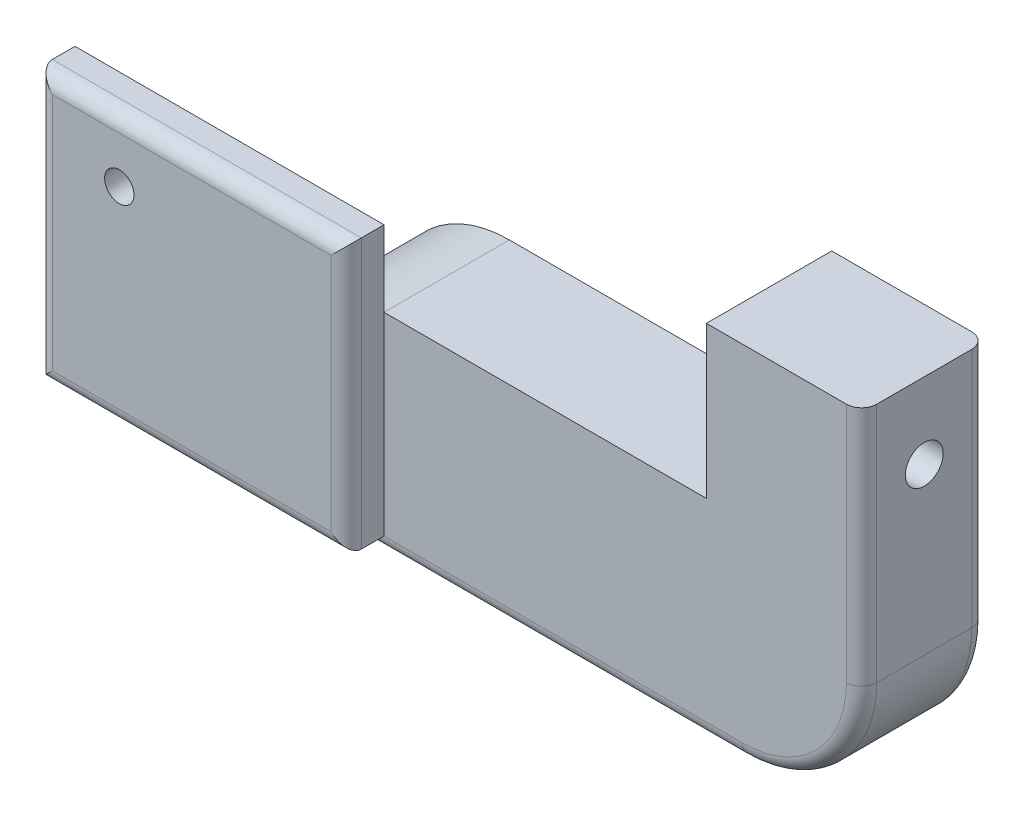
SolidWorks part; units mm, degrees
ref_plane "XY" through (0, 0, 0) normal (0, 0, 1) x (1, 0, 0)
ref_plane "XZ" through (0, 0, 0) normal (0, 1, 0) x (1, 0, 0)
ref_plane "YZ" through (0, 0, 0) normal (1, 0, 0) x (0, 0, -1)
ref_axis "X" through (-88.3595, 0, 0) along (1, 0, 0)
ref_axis "Y" through (0, -20.5837, 0) along (0, 1, 0)
ref_axis "Z" through (0, 0, 28.7175) along (0, 0, -1)
sketch "Sketch1" plane through (0, 0, 0) normal (0, 0, 1) x (1, 0, 0)
  line L1 (-50, -17.5) -> (30, -17.5)
  line L2 (-50, -17.5) -> (-50, -2.5)
  line L3 (-30, 17.5) -> (24, 17.5)
  line L4 (50, 2.5) -> (50, 17.5)
  line L5 (-50, -17.5) -> (50, 17.5) construction
  line L6 (-50, 17.5) -> (50, -17.5) construction
  line L8 (24, 17.5) -> (24, 42.9)
  line L9 (24, 42.9) -> (50, 42.9)
  line L10 (50, 17.5) -> (50, 42.9)
  arc A0 (-50, -2.5) -> (-30, 17.5) centre (-30, -2.5) cw
  arc A1 (30, -17.5) -> (50, 2.5) centre (30, 2.5) ccw
  point P0 (0, 0)
  point P15 (22.6417, 17.9785)
  dimension "D3" = 20
  dimension "D4" = 20
  dimension "D1" = 35
  dimension "D2" = 100
  dimension "D5" = 74
  dimension "D6" = 25.4
extrude "Boss-Extrude1" add sketch "Sketch1" along normal blind 21
fillet "Fillet2" radius 2.54 6 edges at (-10, -17.5, 21) (44.1421, -11.6421, 21) (-10, -17.5, 0) (44.1421, -11.6421, 0) (50, 22.7, 21) (50, 22.7, 0)
sketch "Sketch2" plane through (0, 0, 21) normal (0, 0, 1) x (1, 0, 0)
  line L0 (-50, -14.96) -> (30, -14.96) construction
  line L1 (-30, -14.96) -> (-81.771, -14.96)
  line L2 (-30, -14.96) -> (-30, 30.2)
  line L3 (-30, 30.2) -> (-81.771, 30.2)
  line L4 (-81.771, -14.96) -> (-81.771, 30.2)
  line L5 (24, 17.5) -> (-30, 17.5) construction
  line L6 (-50, -2.5) -> (-50, -14.96) construction
  dimension "D1" = 12.7
  dimension "D2" = 31.771
extrude "Boss-Extrude2" add sketch "Sketch2" along normal blind 6.35
hole_wizard "#8 Clearance Hole1" positions "Sketch3" profile "Sketch5" hole size "#8" standard "ANSI Inch" end condition through all
sketch "Sketch3" plane through (0, 0, 27.35) normal (0, 0, 1) x (1, 0, 0)
  line L0 (-68, 19.9) -> (0, 0)
  point P0 (-68, 19.9)
  dimension "D1" = 68
  dimension "D2" = 19.9
sketch "Sketch5" plane through (-68, 19.9, 27.35) normal (1, 0, 0) x (0, -1, 0)
  line L0 (0, 0) -> (0, 27.35)
  line L1 (0, 27.35) -> (2.4574, 27.35)
  line L2 (2.4574, 27.35) -> (2.4574, 0)
  line L5 (2.4574, 0) -> (0, 0)
  line L11 (0, -6.35) -> (0, 107.95) construction
  dimension "Thru Hole Dia." = 4.9149
  dimension "Thru Hole Depth" = 27.35
fillet "Fillet3" radius 2.54 4 edges at (-81.771, 7.62, 27.35) (-55.8855, -14.96, 27.35) (-30, 7.62, 27.35) (-55.8855, 30.2, 27.35)
hole_wizard "1/4 (0.25) Diameter Hole1" positions "Sketch6" profile "Sketch7" hole size "1/4" standard "ANSI Inch" end condition through all
sketch "Sketch6" plane through (24, 0, 0) normal (-1, 0, 0) x (0, 0, 1)
  line L0 (10.5, 30.2) -> (10.5, 42.9) construction
  line L1 (21, 42.9) -> (0, 42.9) construction
  line L2 (10.5, 42.9) -> (21, 30.2) construction
  line L3 (21, 42.9) -> (21, 17.5) construction
  line L4 (21, 30.2) -> (10.5, 30.2) construction
  point P0 (10.5, 30.2)
sketch "Sketch7" plane through (24, 30.2, 10.5) normal (0, 1, 0) x (0, 0, 1)
  line L0 (0, 0) -> (0, 26)
  line L1 (0, 26) -> (3.175, 26)
  line L2 (3.175, 26) -> (3.175, 0)
  line L5 (3.175, 0) -> (0, 0)
  line L11 (0, -6.35) -> (0, 107.95) construction
  dimension "Thru Hole Dia." = 6.35
  dimension "Thru Hole Depth" = 26
sketch "Sketch8" plane through (24, 0, 0) normal (-1, 0, 0) x (0, 0, 1)
  line L1 (13.7812, 35.8832) -> (7.2188, 35.8832)
  line L2 (7.2188, 35.8832) -> (3.9375, 30.2)
  line L3 (3.9375, 30.2) -> (7.2188, 24.5168)
  line L4 (7.2188, 24.5168) -> (13.7812, 24.5168)
  line L5 (13.7812, 24.5168) -> (17.0625, 30.2)
  line L6 (17.0625, 30.2) -> (13.7812, 35.8832)
  circle A0 centre (10.5, 30.2) radius 5.6832 construction
  dimension "D1" = 11.3665
extrude "Cut-Extrude1" cut sketch "Sketch8" against normal offset from surface (16.475 mm away) 9.525 contours L1 L2 L3 L4 L5 L6 up to face at (50, 30.2, 13.675)
